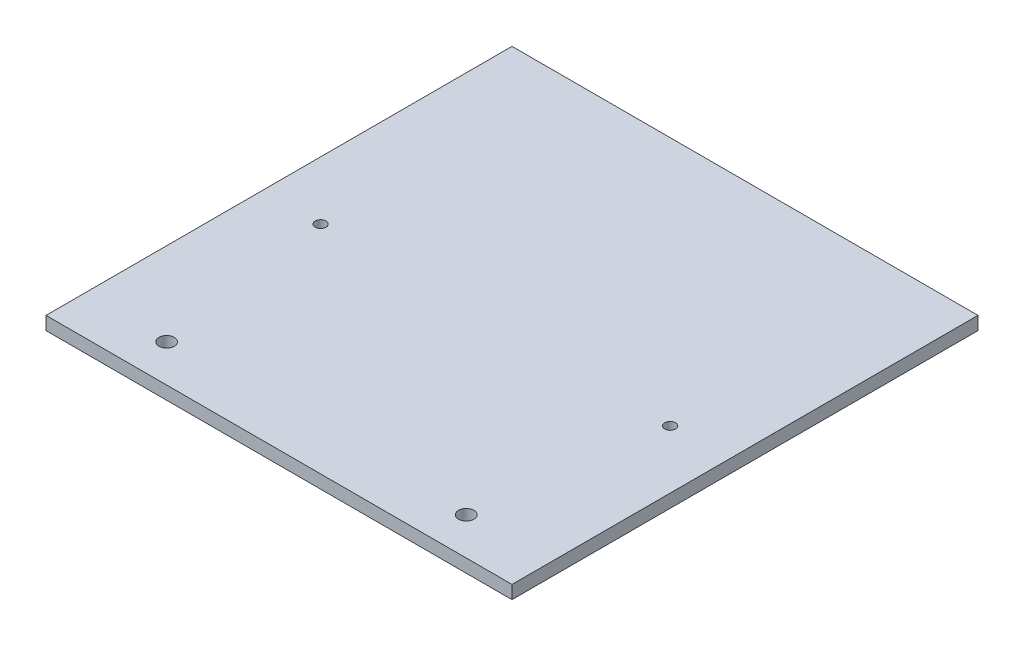
SolidWorks part; units mm, degrees
material "Pin"
ref_plane "Plan de face" through (0, 0, 0) normal (0, 0, 1) x (1, 0, 0)
ref_plane "Plan de dessus" through (0, 0, 0) normal (0, 1, 0) x (1, 0, 0)
ref_plane "Plan de droite" through (0, 0, 0) normal (1, 0, 0) x (0, 0, -1)
sketch "Esquisse1" plane through (0, 0, 0) normal (0, 1, 0) x (1, 0, 0)
  line L1 (-56, 56) -> (56, 56)
  line L2 (-56, 56) -> (-56, -56)
  line L3 (-56, -56) -> (56, -56)
  line L4 (56, 56) -> (56, -56)
  point P4 (0, 56)
  point P6 (-56, 0)
  dimension "D1" = 112
  dimension "D2" = 112
extrude "Boss.-Extru.1" add sketch "Esquisse1" along normal blind 3.175
hole_wizard "Dégagement M41" positions "Esquisse2" profile "Esquisse3" hole size "M4" standard "Ansi Metric"
sketch "Esquisse2" plane through (0, 3.175, 0) normal (0, 1, 0) x (1, 0, 0)
  line L0 (36, -47) -> (-36, -47) construction
  line L1 (-56, -56) -> (56, -56) construction
  point P0 (-36, -47)
  point P13 (36, -47)
  point P20 (0, -47)
  dimension "D1" = 72
  dimension "D2" = 9
sketch "Esquisse3" plane through (-36, 3.175, 47) normal (1, 0, 0) x (0, 0, 1)
  line L0 (0, 0) -> (0, 4.2866)
  line L1 (0, 4.2866) -> (1.85, 3.175)
  line L2 (1.85, 3.175) -> (1.85, 0)
  line L5 (1.85, 0) -> (0, 0)
  line L10 (0, 4.2866) -> (-1.85, 3.175) construction
  line L11 (0, -6.35) -> (0, 107.95) construction
  dimension "Diamètre du perçage" = 3.7
  dimension "Profondeur du perçage" = 3.175
  dimension "Angle de pointe" = 118
sketch "Esquisse4" plane through (0, 3.175, 0) normal (0, 1, 0) x (1, 0, 0)
  line L0 (42, -4) -> (-42, -4) construction
  point P2 (0, -4)
  dimension "D1" = 84
  dimension "D2" = 4
hole_wizard "Dégagement M32" positions "Esquisse7" profile "Esquisse6" hole size "M3" standard "Ansi Metric"
sketch "Esquisse7" plane through (0, 3.175, 0) normal (0, 1, 0) x (1, 0, 0)
  point P0 (42, -4)
  point P3 (-42, -4)
sketch "Esquisse6" plane through (42, 3.175, 4) normal (1, 0, 0) x (0, 0, 1)
  line L0 (0, 0) -> (0, 3.9561)
  line L1 (0, 3.9561) -> (1.3, 3.175)
  line L2 (1.3, 3.175) -> (1.3, 0)
  line L5 (1.3, 0) -> (0, 0)
  line L10 (0, 3.9561) -> (-1.3, 3.175) construction
  line L11 (0, -6.35) -> (0, 107.95) construction
  dimension "Diamètre du perçage" = 2.6
  dimension "Profondeur du perçage" = 3.175
  dimension "Angle de pointe" = 118
